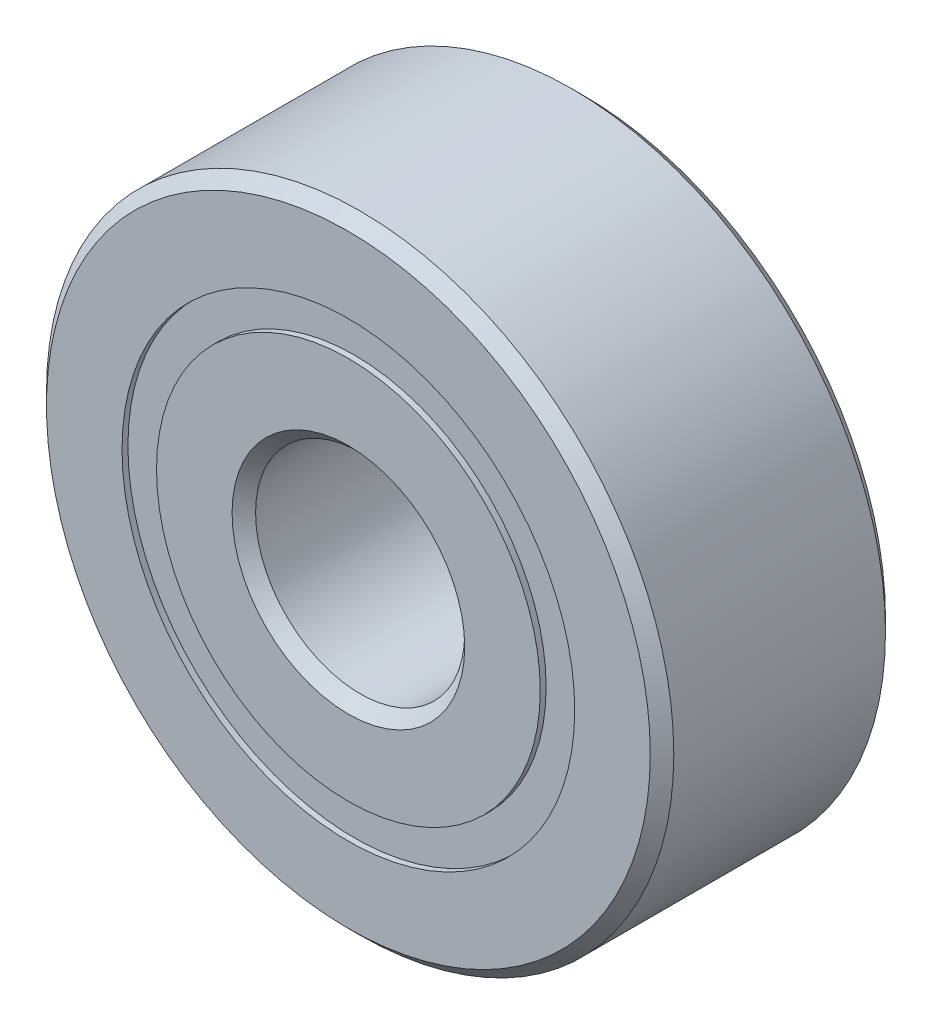
SolidWorks part; units mm, degrees
material "Alloy Steel"
ref_plane "Front Plane" through (0, 0, 0) normal (0, 0, 1) x (1, 0, 0)
ref_plane "Top Plane" through (0, 0, 0) normal (0, 1, 0) x (1, 0, 0)
ref_plane "Right Plane" through (0, 0, 0) normal (1, 0, 0) x (0, 0, -1)
sketch "Sketch1" plane through (0, 0, 0) normal (1, 0, 0) x (0, 0, -1)
  line L0 (-3.5719, 0) -> (3.5719, 0) construction
  line L1 (0, 9.525) -> (0, -9.525) construction
  line L2 (3.2147, 9.525) -> (-3.2147, 9.525)
  line L3 (-3.2147, 9.525) -> (-3.5719, 9.1678)
  line L4 (-3.5719, 9.1678) -> (-3.5719, 6.8734)
  line L5 (-3.5719, 6.8734) -> (-1.5875, 6.8734)
  line L6 (3.5719, 6.8734) -> (1.5875, 6.8734)
  line L7 (3.5719, 9.1678) -> (3.5719, 6.8734)
  line L8 (3.2147, 9.525) -> (3.5719, 9.1678)
  line L9 (0, 9.525) -> (0, 6.35) construction
  line L10 (0, 6.35) -> (0, 3.175) construction
  arc A0 (-1.5875, 6.8734) -> (1.5875, 6.8734) centre (0, 6.35) cw
  point P14 (0, 3.175)
  dimension "Width" = 7.1437
  dimension "OD" = 19.05
  dimension "D1" = 45
  dimension "D2" = 0.3572
  dimension "Shaft Dia" = 6.35
  dimension "D3" = 3.175
  dimension "D4" = 0.5234
revolve "Revolve1" add sketch "Sketch1" angle 360 about L0
sketch "Sketch3" plane through (0, 0, 0) normal (1, 0, 0) x (0, 0, -1)
  line L0 (-3.5719, 5.8266) -> (-1.5875, 5.8266)
  line L1 (0, 9.525) -> (0, -9.525) construction
  line L2 (-3.5719, 9.1678) -> (-3.5719, 6.8734) construction
  line L3 (-3.5719, 5.8266) -> (-3.5719, 3.5322)
  line L4 (-3.2147, 9.525) -> (-3.5719, 9.1678) construction
  line L5 (-3.5719, 3.5322) -> (-3.2147, 3.175)
  line L6 (-3.2147, 3.175) -> (3.2147, 3.175)
  line L7 (3.2147, 9.525) -> (3.2147, -9.525) construction
  line L8 (3.2147, 3.175) -> (3.5719, 3.5322)
  line L9 (3.5719, -9.1678) -> (3.5719, 9.1678) construction
  line L10 (3.5719, 3.5322) -> (3.5719, 5.8266)
  line L11 (3.5719, 5.8266) -> (1.5875, 5.8266)
  line L13 (3.2147, 9.525) -> (3.5719, 9.1678) construction
  arc A0 (1.5875, 6.8734) -> (-1.5875, 6.8734) centre (0, 6.35) ccw construction
  arc A1 (1.5875, 5.8266) -> (-1.5875, 5.8266) centre (0, 6.35) cw
revolve "Revolve3" add sketch "Sketch3" angle 360 about L0
sketch "Sketch4" plane through (0, 0, 0) normal (1, 0, 0) x (0, 0, -1)
  line L0 (-1.6715, 6.35) -> (1.6715, 6.35)
  arc A2 (-1.6715, 6.35) -> (1.6715, 6.35) centre (0, 6.35) cw
  arc A3 (1.5875, 6.8734) -> (-1.5875, 6.8734) centre (0, 6.35) ccw construction
revolve "Revolve4" [suppressed] add sketch "Sketch4" angle 360 about L0
ref_axis "Axis1" [suppressed] through (0, 0, -3.5719) along (0, 0, 1)
pattern_circular "CirPattern1" [suppressed] count 8 every 45 about axis through (0, 0, -3.5719) along (0, 0, 1) of bodies 104
sketch "Sketch5" plane through (0, 0, 0) normal (1, 0, 0) x (0, 0, -1)
  line L0 (-3.5719, 6.8734) -> (-1.5875, 6.8734) construction
  line L1 (-3.3933, 6.8734) -> (-1.6715, 6.8734)
  line L2 (-3.3933, 6.8734) -> (-3.3933, 5.8266)
  line L3 (-3.3933, 5.8266) -> (-1.6715, 5.8266)
  line L4 (-1.6715, 6.8734) -> (-1.6715, 5.8266)
  line L5 (-3.5719, 5.8266) -> (-1.5875, 5.8266) construction
  line L6 (3.5719, 6.8734) -> (1.5875, 6.8734) construction
  line L7 (3.3933, 6.8734) -> (1.6715, 6.8734)
  line L8 (3.3933, 6.8734) -> (3.3933, 5.8266)
  line L9 (3.3933, 5.8266) -> (1.6715, 5.8266)
  line L10 (1.6715, 6.8734) -> (1.6715, 5.8266)
  line L11 (3.5719, 5.8266) -> (1.5875, 5.8266) construction
  line L12 (-3.2147, 9.525) -> (-3.5719, 9.1678) construction
  point P18 (-3.3933, 9.3464)
revolve "Revolve5" add sketch "Sketch5" angle 360 about L0
equation "\"D2@Sketch1\" = \"Width@Sketch1\"*.05"
equation "\"D3@Sketch1\" = \"Width@Sketch1\"/2.25"
equation "\"D4@Sketch1\" = (((\"OD@Sketch1\"-\"Width@Sketch1\")/2)/3.25)/3.5"
equation "\"D2@CirPattern1\" = 360/\"Balls@CirPattern1\""
